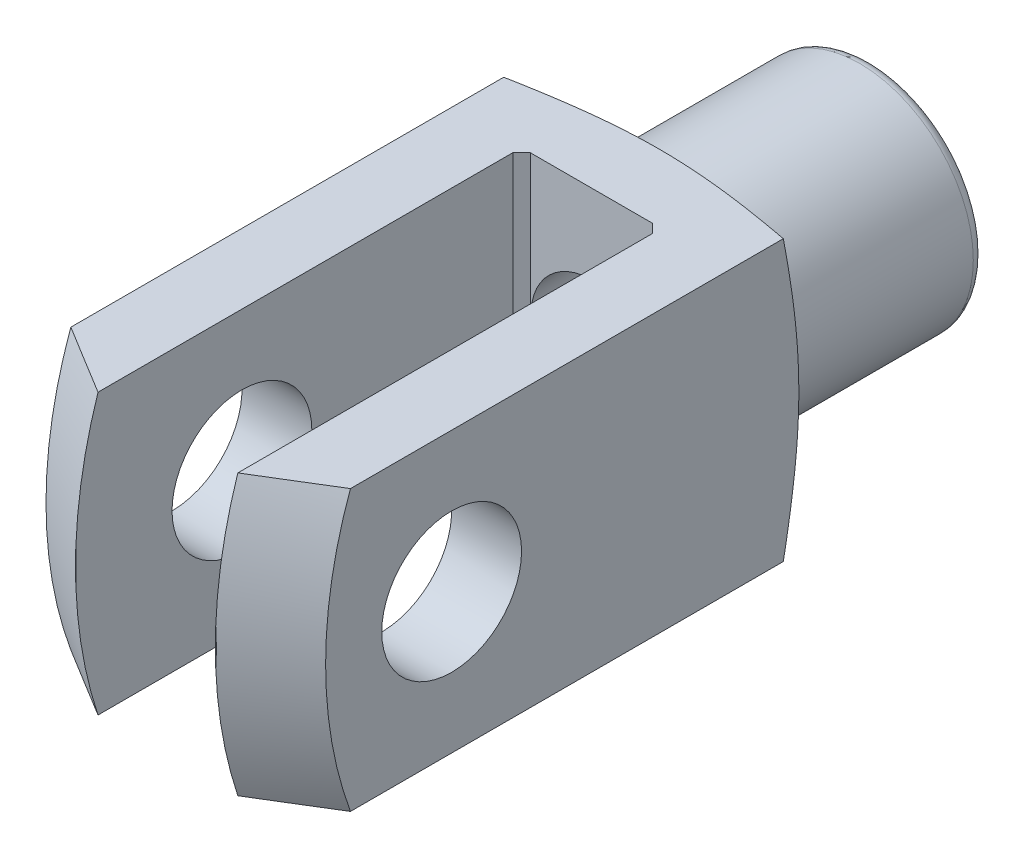
SolidWorks part; units mm, degrees
ref_plane "Front Plane" through (0, 0, 0) normal (0, 0, 1) x (1, 0, 0)
ref_plane "Top Plane" through (0, 0, 0) normal (0, 1, 0) x (1, 0, 0)
ref_plane "Right Plane" through (0, 0, 0) normal (1, 0, 0) x (0, 0, -1)
ref_plane "Plane1" through (0, 0, 0) normal (1, 0, 0) x (0, 0, -1)
sketch "Sketch1" plane through (0, 0, 0) normal (1, 0, 0) x (0, 0, -1)
  line L0 (-19, 0) -> (-19, 32)
  line L1 (-19, 32) -> (35.4449, 32)
  line L2 (35.4449, 32) -> (40, 15)
  line L3 (42, 13) -> (62.7, 13)
  line L4 (64, 11.7) -> (64, 0)
  line L5 (64, 0) -> (-19, 0)
  line L6 (64, 0) -> (-19, 0) construction
  arc A0 (40, 15) -> (42, 13) centre (42, 15) ccw
  arc A1 (62.7, 13) -> (64, 11.7) centre (62.7, 11.7) cw
revolve "Revolve1" add sketch "Sketch1" angle 360 about L6 reverse direction yes
ref_plane "Plane2" through (0, 0, 0) normal (0, 1, 0) x (1, 0, 0)
sketch "Sketch2" plane through (0, 0, 0) normal (0, 1, 0) x (1, 0, 0)
  line L0 (-8, 31) -> (-8, -20)
  line L1 (-8, -20) -> (8, -20)
  line L2 (8, -20) -> (8, 31)
  line L3 (8, 31) -> (7, 32)
  line L4 (7, 32) -> (-7, 32)
  line L5 (-7, 32) -> (-8, 31)
extrude "Cut-Extrude1" cut sketch "Sketch2" against normal blind 33 and the other way blind 33
ref_plane "Plane3" through (0, 0, 0) normal (1, 0, 0) x (0, 0, -1)
sketch "Sketch3" plane through (0, 0, 0) normal (1, 0, 0) x (0, 0, -1)
  line L0 (-52, -48) -> (64, -48)
  line L1 (64, -48) -> (64, -16)
  line L2 (64, -16) -> (-20, -16)
  line L3 (-20, -16) -> (-20, 16)
  line L4 (-20, 16) -> (64, 16)
  line L5 (64, 16) -> (64, 48)
  line L6 (64, 48) -> (-52, 48)
  line L7 (-52, 48) -> (-52, -48)
extrude "Cut-Extrude2" cut sketch "Sketch3" against normal blind 33 and the other way blind 33
ref_plane "Plane4" through (0, 0, 0) normal (0, 1, 0) x (1, 0, 0)
sketch "Sketch4" plane through (0, 0, 0) normal (0, 1, 0) x (1, 0, 0)
  line L0 (-48, -52) -> (48, -52)
  line L1 (48, -52) -> (48, 64)
  line L2 (48, 64) -> (16, 64)
  line L3 (16, 64) -> (16, -20)
  line L4 (16, -20) -> (-16, -20)
  line L5 (-16, -20) -> (-16, 64)
  line L6 (-16, 64) -> (-48, 64)
  line L7 (-48, 64) -> (-48, -52)
extrude "Cut-Extrude3" cut sketch "Sketch4" against normal blind 33 and the other way blind 33
ref_plane "Plane5" through (0, 0, 0) normal (0, 0, 1) x (1, 0, 0)
sketch "Sketch5" plane through (0, 0, 0) normal (0, 0, 1) x (1, 0, 0)
  line L0 (-19.75, 0) -> (-19.75, 8)
  line L1 (-19.75, 8) -> (19.75, 8)
  line L2 (19.75, 8) -> (19.75, 0)
  line L3 (19.75, 0) -> (-19.75, 0)
  line L4 (19.75, 0) -> (-19.75, 0) construction
revolve "Cut-Revolve1" cut sketch "Sketch5" angle 360 about L4 reverse direction yes
ref_plane "Plane6" through (0, 0, 0) normal (1, 0, 0) x (0, 0, -1)
sketch "Sketch6" plane through (0, 0, 0) normal (1, 0, 0) x (0, 0, -1)
  line L0 (30.9, 0) -> (30.9, 6.9175)
  line L1 (30.9, 6.9175) -> (63.0175, 6.9175)
  line L2 (63.0175, 6.9175) -> (64.1, 8)
  line L3 (64.1, 8) -> (64.1, 0)
  line L4 (64.1, 0) -> (30.9, 0)
  line L5 (64.1, 0) -> (30.9, 0) construction
revolve "Cut-Revolve2" cut sketch "Sketch6" angle 360 about L5 reverse direction yes
cosmetic thread "Cosmetic Thread1" parameters "D1"=28.2, "D2"=16
ref_plane "Plane7" through (0, 0, 0) normal (0, 1, 0) x (1, 0, 0)
sketch "Sketch7" plane through (0, 0, 0) normal (0, 1, 0) x (1, 0, 0)
  line L0 (-19, -49.6418) -> (0, -60.6115)
  line L1 (0, -60.6115) -> (19, -49.6418)
  line L2 (19, -49.6418) -> (19, -12.6914)
  line L3 (19, -12.6914) -> (0, -23.6611)
  line L4 (0, -23.6611) -> (-19, -12.6914)
  line L5 (-19, -12.6914) -> (-19, -49.6418)
  line L6 (-19, 32) -> (19, 32) construction
revolve "Cut-Revolve3" cut sketch "Sketch7" angle 90 about L6 other way angle 90 reverse direction yes
